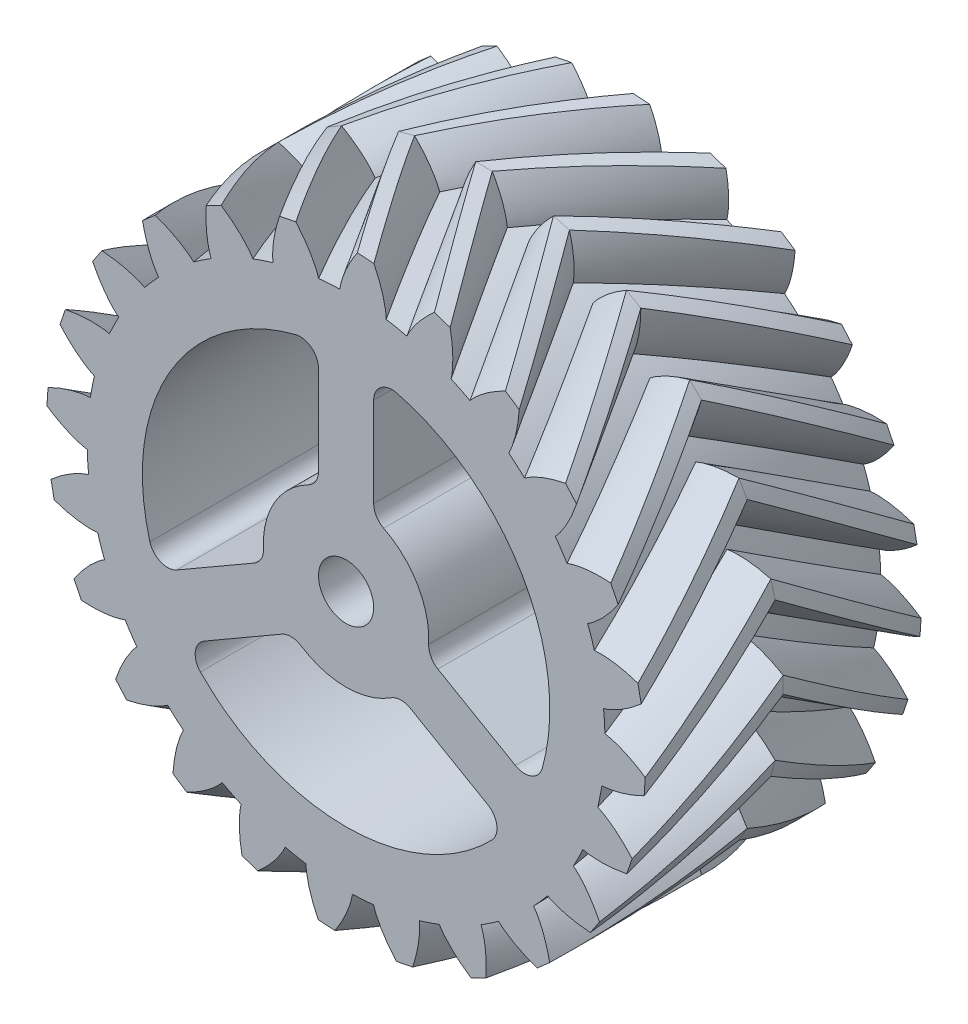
SolidWorks part; units mm, degrees
material "ABS"
ref_plane "Front Plane" through (0, 0, 0) normal (0, 0, 1) x (1, 0, 0)
ref_plane "Top Plane" through (0, 0, 0) normal (0, 1, 0) x (1, 0, 0)
ref_plane "Right Plane" through (0, 0, 0) normal (1, 0, 0) x (0, 0, -1)
sketch "Definition Drawing" plane through (0, 0, 0) normal (0, 0, 1) x (1, 0, 0)
  line L0 (16.2789, 0) -> (14.2789, 0) construction
  line L1 (0, 0) -> (-6.9516, 11.976) construction
  line L2 (0, 0) -> (0, 16.2789) construction
  line L3 (0, 0) -> (1.2743, 13.7886) construction
  line L4 (-6.9516, 11.976) -> (0.4506, 16.2726) construction
  line L5 (0, 0) -> (0.9494, 15.2493) construction
  line L6 (0, 0) -> (0.9993, 15.2462) construction
  line L7 (0, 0) -> (-5.0256, 12.9032) construction
  line L8 (-5.0256, 12.9032) -> (0.9558, 15.2329) construction
  line L9 (0, 0) -> (-2.9798, 13.5229) construction
  line L10 (-2.9798, 13.5229) -> (1.1993, 14.4438) construction
  line L11 (0, 0) -> (-0.8631, 13.8204) construction
  line L12 (-0.8631, 13.8204) -> (1.2725, 13.9538) construction
  circle A0 centre (0, 0) radius 13.8474 construction
  circle A1 centre (0, 0) radius 14.2789 construction
  circle A2 centre (0, 0) radius 15.2789 construction
  circle A3 centre (0, 0) radius 16.2789 construction
  circle A4 centre (0, 0) radius 14.0789 construction
  arc A5 (0.9494, 15.2493) -> (0.9993, 15.2462) centre (0, 0) cw construction
  spline S0 degree 3 poles (1.2743, 13.7886) (1.2817, 14.0092) (1.1458, 14.8862) (0.7794, 15.701) (0.4506, 16.2726) knots 0 0 0 0 0.250019 1 1 1 1 construction
  point P13 (15.2789, 0)
  dimension "D4" = 30.5577
  dimension "D5" = 27.6947
  dimension "D2" = 0.2
  dimension "D3" = 3.75
  dimension "D6" = 0.05
  dimension "D7" = 35.413
  dimension "D11" = 6.4191
  dimension "D12" = 4.2794
  dimension "D13" = 2.1397
  dimension "D8" = 26.56
  dimension "D9" = 17.707
  dimension "D10" = 8.853
sketch "Sketch5" plane through (0, 0, 0) normal (0, 0, 1) x (1, 0, 0)
  circle A1 centre (0, 0) radius 14.0789
  circle A2 centre (0, 0) radius 1.5
  circle A3 centre (0, 0) radius 14.0789 construction
  dimension "D1" = 3
extrude "Extrude Body" add sketch "Sketch5" along normal blind 7.5
sketch "Sketch7" plane through (0, 0, 0) normal (0, 0, 1) x (1, 0, 0)
  circle A0 centre (0, 0) radius 14.0789
  circle A1 centre (0, 0) radius 14.0789 construction
curve "Tooth Helix" pitch 144 height 7.5 radius 14.0789 left hand yes centre (0, 0, 0) axis (0, 0, 1) start towards (0, 1, 0)
sketch "Sketch6" plane through (0, 0, 0) normal (0, 0, 1) x (1, 0, 0)
  line L0 (0, 16.2789) -> (0, 0) construction
  line L4 (1.2743, 13.7886) -> (0.138, 1.4936)
  line L5 (0, 0) -> (1.2743, 13.7886) construction
  line L6 (-1.2743, 13.7886) -> (-0.138, 1.4936)
  arc A0 (0.4506, 16.2726) -> (-0.4506, 16.2726) centre (0, 0) ccw
  arc A3 (0.138, 1.4936) -> (-0.138, 1.4936) centre (0, 0) ccw
  circle A4 centre (0, 0) radius 1.5 construction
  spline S0 degree 3 poles (1.2743, 13.7886) (1.2817, 14.0092) (1.1458, 14.8862) (0.7794, 15.701) (0.4506, 16.2726) knots 0 0 0 0 0.250019 1 1 1 1
  spline S1 degree 3 poles (-1.2743, 13.7886) (-1.2817, 14.0092) (-1.1458, 14.8862) (-0.7794, 15.701) (-0.4506, 16.2726) knots 0 0 0 0 0.250019 1 1 1 1
sweep "Sweep Half Tooth" add profiles "Sketch6" path "Tooth Helix"
pattern_circular "Pattern Half Teeth" count 24 over 360 about axis through (0, 0, 7.5) along (0, 0, -1) of "Sweep Half Tooth"
sketch "Sketch8" plane through (0, 0, 0) normal (0, 0, 1) x (1, 0, 0)
  line L6 (0, 16.2789) -> (0, 0) construction
  line L7 (0, 0) -> (14.0979, -8.1394) construction
  line L8 (1.5, 9.7639) -> (1.5, 4.899)
  line L9 (4.9926, -1.1505) -> (9.2058, -3.5829)
  circle A2 centre (0, 0) radius 16.2789 construction
  arc A20 (10.6688, -2.9864) -> (2.748, 10.7326) centre (0, 0) ccw
  circle A21 centre (0, 0) radius 14.0789 construction
  arc A23 (9.2058, -3.5829) -> (10.6688, -2.9864) centre (9.7058, -2.7169) ccw
  arc A24 (4.9926, -1.1505) -> (4.494, -0.2327) centre (5.4926, -0.2844) cw
  arc A25 (1.5, 4.899) -> (2.0455, 4.0083) centre (2.5, 4.899) ccw
  arc A26 (1.5, 9.7639) -> (2.748, 10.7326) centre (2.5, 9.7639) cw
  arc A27 (4.494, -0.2327) -> (2.0455, 4.0083) centre (0, 0) ccw
  circle A28 centre (0, 0) radius 1.5 construction
  dimension "D1" = 3
  dimension "D6" = 1
  dimension "D4" = 3
  dimension "D5" = 3
  dimension "D2" = 3
  dimension "D3" = 120
extrude "Cut Spoke" cut sketch "Sketch8" against normal through all and the other way through all
pattern_circular "Pattern Spokes" count 3 over 360 about axis through (0, 0, 7.5) along (0, 0, -1) of "Cut Spoke"
mirror "Mirror Body" about plane through (0, 0, 0) normal (0, 0, 1) of bodies 134
equation "\"nTeeth\" = 24"
equation "\"xThickness\"= 15"
equation "\"dShaft\"= 3"
equation "\"aPressure\"=25"
equation "\"pitch\"= 4"
equation "\"rHeight\"= 2"
equation "\"rClearance\"= 0.2"
equation "\"xClearance\"=0.05"
equation "\"rFillet\"= 1"
equation "\"nSpokes\"= int ( ( \"nTeeth\" - 1 ) / 10 ) + 1'rounds up"
equation "\"dPitch\"= \"nTeeth\" * \"pitch\" / pi"
equation "\"xWall\"= IIF ( \"nTeeth\" > 30 , \"nTeeth\" / 10 , 3 )"
equation "\"dBase\"= \"dPitch\" * cos ( \"aPressure\" )"
equation "\"rOuter\"= \"dPitch\" / 2 + \"rHeight\" / 2"
equation "\"xInvolute\"= sqr ( \"rOuter\" ^ 2 - ( \"dBase\" / 2 ) ^ 2 )"
equation "\"aInvolute\"= 360 * \"xInvolute\" / ( \"dBase\" / 2 ) / 2 / pi"
equation "\"xSkew\"= \"xThickness\" / 3"
equation "\"D1@Definition Drawing\" = \"rHeight\""
equation "\"D2@Definition Drawing\" = \"rClearance\""
equation "\"D4@Definition Drawing\" = \"dPitch\""
equation "\"D6@Definition Drawing\" = \"xClearance\""
equation "\"D5@Definition Drawing\" = \"dBase\""
equation "\"D7@Definition Drawing\" = \"aInvolute\""
equation "\"D11@Definition Drawing\" = \"xInvolute\" * 0.75"
equation "\"D12@Definition Drawing\" = \"xInvolute\" * 0.5"
equation "\"D13@Definition Drawing\" = \"xInvolute\" * 0.25"
equation "\"D8@Definition Drawing\" = \"aInvolute\" * 0.75"
equation "\"D9@Definition Drawing\" = \"aInvolute\" * 0.5"
equation "\"D10@Definition Drawing\" = \"aInvolute\" * 0.25"
equation "\"D1@Extrude Body\"=\"xThickness\"/2"
equation "\"D1@Sketch5\"=\"dShaft\""
equation "\"D5@Tooth Helix\" = \"xSkew\" /  ( \"dPitch\" * pi ) "
equation "\"D3@Tooth Helix\" = \"xThickness\" / 2"
equation "\"D7@Tooth Helix\" = 90.00deg"
equation "\"D3@Definition Drawing\" = 360 / \"nTeeth\" / 2 / 2"
equation "\"D5@Sketch8\"=\"xWall\""
equation "\"D1@Sketch8\"=\"xWall\""
equation "\"D4@Sketch8\"=\"xWall\""
equation "\"D6@Sketch8\"=\"rFillet\""
equation "\"D1@Pattern Spokes\" = \"nSpokes\""
equation "\"rHub\"= IIF ( \"xWall\" * \"nSpokes\" / 6 > \"xWall\" , \"xWall\" * \"nSpokes\" / 6 , \"xWall\" )"
equation "\"D1@Pattern Half Teeth\" = \"nTeeth\""
equation "\"D2@Sketch8\"=\"rHub\""
equation "\"D3@Sketch8\"=360/\"nSpokes\""
